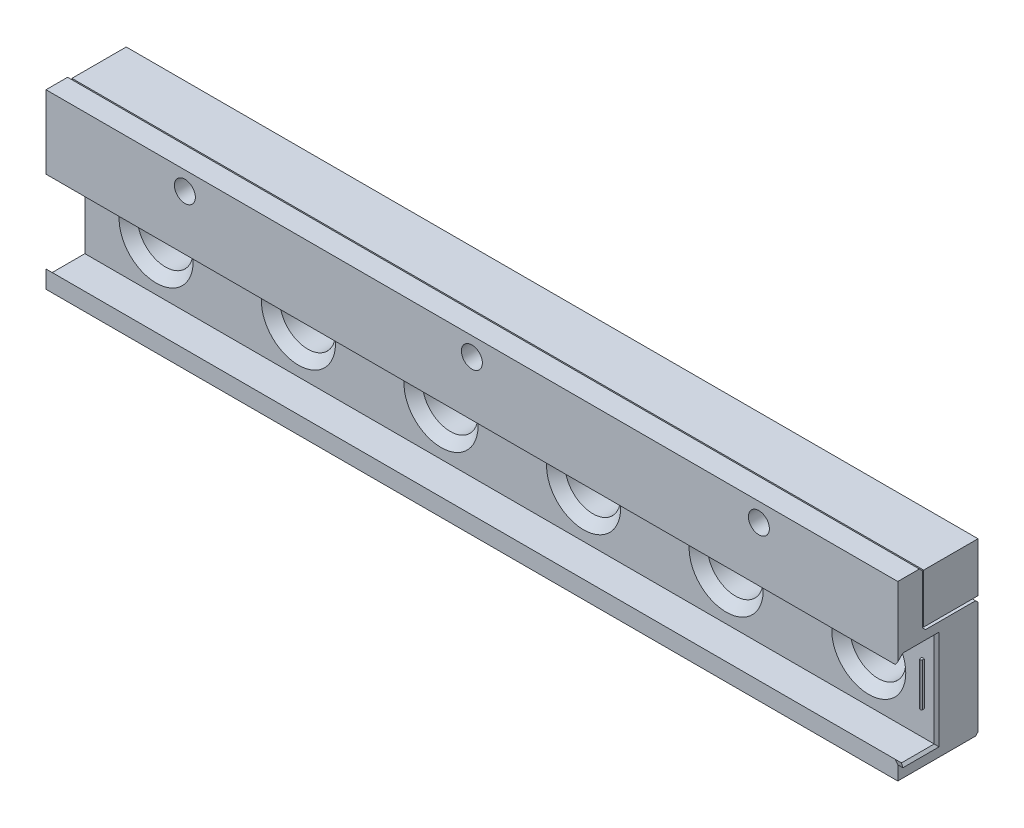
SolidWorks part; units mm, degrees
ref_plane "Front Plane" through (0, 0, 0) normal (0, 0, 1) x (1, 0, 0)
ref_plane "Top Plane" through (0, 0, 0) normal (0, 1, 0) x (1, 0, 0)
ref_plane "Right Plane" through (0, 0, 0) normal (1, 0, 0) x (0, 0, -1)
sketch "Sketch1" plane through (0, 0, 0) normal (0, 0, 1) x (1, 0, 0)
  line L1 (-107.1072, 25.5521) -> (30.8928, 25.5521)
  line L2 (-107.1072, 25.5521) -> (-107.1072, 6.5521)
  line L3 (-107.1072, 6.5521) -> (30.8928, 6.5521)
  line L4 (30.8928, 25.5521) -> (30.8928, 6.5521)
  dimension "D1" = 138
  dimension "D2" = 19
extrude "Boss-Extrude1" add sketch "Sketch1" along normal blind 13
sketch "Sketch2" plane through (0, 0, 13) normal (0, 0, 1) x (1, 0, 0)
  line L0 (-107.1072, 25.5521) -> (-107.1072, 6.5521) construction
  line L1 (-107.1072, 6.5521) -> (30.8928, 6.5521) construction
  circle A0 centre (-95.5572, 16.0521) radius 4.5
  dimension "D1" = 9
  dimension "D2" = 11.55
  dimension "D3" = 9.5
extrude "Cut-Extrude1" cut sketch "Sketch2" against normal through all
sketch "Sketch4" plane through (0, 0, 13) normal (0, 0, 1) x (1, 0, 0)
  line L0 (-107.1072, 6.5521) -> (30.8928, 6.5521) construction
  circle A0 centre (-72.5072, 16.0521) radius 4.5
  circle A1 centre (-95.5572, 16.0521) radius 4.5 construction
  dimension "D2" = 9
  dimension "D1" = 23.05
  dimension "D3" = 9.5
extrude "Cut-Extrude2" cut sketch "Sketch4" against normal through all
sketch "Sketch5" plane through (0, 0, 13) normal (0, 0, 1) x (1, 0, 0)
  line L0 (-107.1072, 6.5521) -> (30.8928, 6.5521) construction
  circle A0 centre (-49.4072, 16.0521) radius 4.5
  circle A1 centre (-72.5072, 16.0521) radius 4.5 construction
  dimension "D2" = 9
  dimension "D1" = 23.1
  dimension "D3" = 9.5
extrude "Cut-Extrude3" cut sketch "Sketch5" against normal through all
sketch "Sketch6" plane through (0, 0, 13) normal (0, 0, 1) x (1, 0, 0)
  line L0 (-107.1072, 6.5521) -> (30.8928, 6.5521) construction
  circle A0 centre (-26.3072, 16.0521) radius 4.5
  circle A1 centre (-49.4072, 16.0521) radius 4.5 construction
  circle A2 centre (-3.2072, 16.0521) radius 4.5
  circle A3 centre (19.8928, 16.0521) radius 4.5
  dimension "D3" = 9
  dimension "D6" = 9
  dimension "D9" = 9
  dimension "D1" = 23.1
  dimension "D2" = 9.5
  dimension "D4" = 23.1
  dimension "D5" = 9.5
  dimension "D7" = 23.1
  dimension "D8" = 9.5
extrude "Cut-Extrude4" cut sketch "Sketch6" against normal through all
sketch "Sketch7" plane through (0, 0, 13) normal (0, 0, 1) x (1, 0, 0)
  line L0 (-107.1072, 25.5521) -> (-107.1072, 6.5521) construction
  line L1 (-107.1072, 23.7021) -> (30.8928, 23.7021)
  line L2 (-107.1072, 23.7021) -> (-107.1072, 8.4021)
  line L3 (-107.1072, 8.4021) -> (30.8928, 8.4021)
  line L4 (30.8928, 23.7021) -> (30.8928, 8.4021)
  line L5 (30.8928, 6.5521) -> (30.8928, 25.5521) construction
  line L6 (30.8928, 25.5521) -> (-107.1072, 25.5521) construction
  line L7 (-107.1072, 6.5521) -> (30.8928, 6.5521) construction
  dimension "D1" = 1.85
  dimension "D2" = 1.85
extrude "Cut-Extrude5" cut sketch "Sketch7" against normal blind 6.3
sketch "Sketch11" plane through (0, 25.5521, 0) normal (0, 1, 0) x (1, 0, 0)
  line L0 (30.8928, -13) -> (30.8928, 0) construction
  line L1 (-107.1072, -13) -> (30.8928, -13)
  line L2 (-107.1072, -13) -> (-107.1072, -9)
  line L3 (-107.1072, -9) -> (30.8928, -9)
  line L4 (30.8928, -13) -> (30.8928, -9)
  dimension "D1" = 4
extrude "Boss-Extrude4" add sketch "Sketch11" along normal blind 9
sketch "Sketch12" plane through (0, 0, 13) normal (0, 0, 1) x (1, 0, 0)
  line L0 (-107.1072, 34.5521) -> (30.8928, 34.5521) construction
  line L1 (-107.1072, 34.5521) -> (-107.1072, 23.7021) construction
  circle A0 centre (-84.6072, 31.5521) radius 1.7
  dimension "D1" = 3.4
  dimension "D2" = 3
  dimension "D3" = 22.5
extrude "Cut-Extrude6" cut sketch "Sketch12" against normal through all
sketch "Sketch13" plane through (0, 0, 13) normal (0, 0, 1) x (1, 0, 0)
  line L0 (-107.1072, 34.5521) -> (30.8928, 34.5521) construction
  line L1 (30.8928, 23.7021) -> (30.8928, 34.5521) construction
  circle A0 centre (8.3928, 31.5521) radius 1.7
  dimension "D1" = 3.4
  dimension "D2" = 3
  dimension "D3" = 22.5
extrude "Cut-Extrude7" cut sketch "Sketch13" against normal through all
chamfer "Chamfer1" distance 0.4 angle 45 2 edges at (-38.1072, 25.5521, 0) (-38.1072, 6.5521, 0)
chamfer "Chamfer2" distance 0.5 angle 45 2 edges at (-82.9072, 31.5521, 9) (10.0928, 31.5521, 9)
chamfer "Chamfer3" distance 0.5 angle 45 1 edges at (-38.1072, 25.5521, 9)
chamfer "Chamfer4" distance 0.5 angle 45 1 edges at (-38.1072, 34.5521, 9)
sketch "Sketch14" plane through (0, 0, 0) normal (0, 0, -1) x (-1, 0, 0)
  line L1 (-30.8928, 34.0521) -> (107.1072, 34.0521)
  line L2 (-30.8928, 34.0521) -> (-30.8928, 26.0521)
  line L3 (-30.8928, 26.0521) -> (107.1072, 26.0521)
  line L4 (107.1072, 34.0521) -> (107.1072, 26.0521)
extrude "Boss-Extrude5" add sketch "Sketch14" against normal blind 8.8 separate body
sketch "Sketch15" plane through (0, 0, 8.8) normal (0, 0, 1) x (1, 0, 0)
  line L0 (-107.1072, 34.0521) -> (30.8928, 34.0521) construction
  line L1 (-106.1072, 33.0521) -> (29.8928, 33.0521)
  line L2 (-106.1072, 33.0521) -> (-106.1072, 27.0521)
  line L3 (-106.1072, 27.0521) -> (29.8928, 27.0521)
  line L4 (29.8928, 33.0521) -> (29.8928, 27.0521)
  line L5 (30.8928, 26.0521) -> (-107.1072, 26.0521) construction
  line L6 (-107.1072, 26.0521) -> (-107.1072, 34.0521) construction
  line L7 (30.8928, 34.0521) -> (30.8928, 26.0521) construction
  dimension "D1" = 1
  dimension "D2" = 1
  dimension "D3" = 1
  dimension "D4" = 1
extrude "Cut-Extrude8" cut sketch "Sketch15" against normal blind 1
chamfer "Chamfer5" distance 1.5 angle 45 4 edges at (-21.8072, 16.0521, 6.7) (-44.9072, 16.0521, 6.7) (-68.0072, 16.0521, 6.7) (-91.0572, 16.0521, 6.7)
sketch "Sketch19" plane through (30.8928, 0, 0) normal (1, 0, 0) x (0, 0, -1)
  line L0 (-13, 23.7021) -> (-12, 23.7021)
  line L1 (-6.7, 23.7021) -> (-13, 23.7021) construction
  line L2 (-12, 23.7021) -> (-13, 22.7021)
  line L3 (-13, 22.7021) -> (-13, 23.7021)
  line L4 (-13, 8.4021) -> (-12, 8.4021)
  line L5 (-6.7, 8.4021) -> (-13, 8.4021) construction
  line L6 (-12, 8.4021) -> (-13, 9.4021)
  line L7 (-13, 9.4021) -> (-13, 8.4021)
  dimension "D1" = 1
  dimension "D2" = 1
  dimension "D3" = 1
extrude "Boss-Extrude8" add sketch "Sketch19" against normal up to surface (138 mm away) up to face at (-107.1072, 20.695, 7.3)
sketch "Sketch20" plane through (0, 0, 6.7) normal (0, 0, 1) x (1, 0, 0)
  line L1 (28.4928, 19.5521) -> (28.8928, 19.5521)
  line L2 (28.4928, 19.5521) -> (28.4928, 12.5521)
  line L3 (28.4928, 12.5521) -> (28.8928, 12.5521)
  line L4 (28.8928, 19.5521) -> (28.8928, 12.5521)
  line L5 (30.8928, 23.7021) -> (-107.1072, 23.7021) construction
  line L6 (30.8928, 8.4021) -> (30.8928, 23.7021) construction
  dimension "D1" = 0.4
  dimension "D2" = 7
  dimension "D3" = 2
  dimension "D4" = 4.15
chamfer "Chamfer6" distance 0.4 angle 45 5 edges at (30.8928, 23.2021, 12.5) (30.8928, 23.7021, 9.35) (30.8928, 16.0521, 6.7) (30.8928, 8.4021, 9.35) (30.8928, 8.9021, 12.5)
extrude "Boss-Extrude9" add sketch "Sketch20" along normal blind 0.75
fillet "Fillet1" radius 0.5 1 edges at (28.4928, 16.0521, 7.45)
fillet "Fillet2" radius 0.2 1 edges at (28.8928, 16.0521, 7.45)
chamfer "Chamfer7" distance 1.5 angle 45 2 edges at (24.3928, 16.0521, 6.7) (1.2928, 16.0521, 6.7)
sketch "Sketch25" plane through (0, 0, 13) normal (0, 0, 1) x (1, 0, 0)
  line L0 (-107.1072, 34.5521) -> (30.8928, 34.5521) construction
  circle A2 centre (-38.1072, 31.5521) radius 1.7
  dimension "D2" = 3.4
  dimension "D3" = 3
extrude "Cut-Extrude9" cut sketch "Sketch25" against normal blind 4
chamfer "Chamfer8" distance 0.4 angle 45 1 edges at (-36.4072, 31.5521, 9)
sketch "Sketch26" plane through (0, 0, 0) normal (0, 0, -1) x (-1, 0, 0)
  line L0 (107.1072, 34.0521) -> (-30.8928, 34.0521) construction
  line L1 (-29.8928, 33.0521) -> (106.1072, 33.0521)
  line L2 (-29.8928, 33.0521) -> (-29.8928, 27.0521)
  line L3 (-29.8928, 27.0521) -> (106.1072, 27.0521)
  line L4 (106.1072, 33.0521) -> (106.1072, 27.0521)
  line L5 (-30.8928, 26.0521) -> (107.1072, 26.0521) construction
  line L6 (-30.8928, 34.0521) -> (-30.8928, 26.0521) construction
  line L7 (107.1072, 26.0521) -> (107.1072, 34.0521) construction
  dimension "D1" = 1
  dimension "D2" = 1
  dimension "D3" = 1
  dimension "D4" = 1
extrude "Cut-Extrude10" cut sketch "Sketch26" against normal blind 7
sketch "Sketch27" plane through (0, 0, 8.8) normal (0, 0, 1) x (1, 0, 0)
  line L0 (-106.1072, 33.0521) -> (-105.1072, 33.0521)
  line L1 (29.8928, 33.0521) -> (-106.1072, 33.0521) construction
  line L2 (-105.1072, 33.0521) -> (-100.906, 27.0521)
  line L3 (-106.1072, 27.0521) -> (29.8928, 27.0521) construction
  line L4 (-100.906, 27.0521) -> (-101.906, 27.0521)
  line L5 (-106.1072, 27.0521) -> (29.8928, 27.0521) construction
  line L6 (-101.906, 27.0521) -> (-106.1072, 33.0521)
  line L7 (-106.1072, 33.0521) -> (-106.1072, 27.0521) construction
  dimension "D1" = 1
  dimension "D2" = 1
  dimension "D3" = 35
extrude "Boss-Extrude10" add sketch "Sketch27" against normal up to surface (1 mm away) up to face at (-38.1072, 30.0521, 7.8)
sketch "Sketch28" plane through (0, 0, 8.8) normal (0, 0, 1) x (1, 0, 0)
  line L0 (-106.1072, 27.0521) -> (-105.1072, 27.0521)
  line L1 (-106.1072, 27.0521) -> (-101.906, 27.0521) construction
  line L2 (-105.1072, 27.0521) -> (-100.906, 33.0521)
  line L3 (29.8928, 33.0521) -> (-105.1072, 33.0521) construction
  line L4 (-100.906, 33.0521) -> (-101.906, 33.0521)
  line L5 (29.8928, 33.0521) -> (-105.1072, 33.0521) construction
  line L6 (-101.906, 33.0521) -> (-106.1072, 27.0521)
  line L7 (-106.1072, 33.0521) -> (-106.1072, 27.0521) construction
  dimension "D1" = 1
  dimension "D2" = 1
  dimension "D3" = 35
extrude "Boss-Extrude11" add sketch "Sketch28" against normal up to surface (1 mm away) up to face at (-36.5569, 30.0521, 7.8)
pattern_linear "LPattern1" count 27 spacing 5.2 along (1, 0, 0) of "Boss-Extrude11", "Boss-Extrude10"
sketch "Sketch29" plane through (30.8928, 0, 0) normal (1, 0, 0) x (0, 0, -1)
  line L0 (-8.8, 26.0521) -> (0, 26.0521) construction
  line L1 (-8.8, 34.0521) -> (-7.7774, 34.0521)
  line L2 (-8.8, 34.0521) -> (-8.8, 26.0521)
  line L3 (-8.8, 26.0521) -> (-7.7774, 26.0521)
  line L4 (-7.7774, 34.0521) -> (-7.7774, 26.0521)
extrude "Cut-Extrude11" cut sketch "Sketch29" along normal blind 6.9
sketch "Sketch30" plane through (0, 0, 0) normal (0, 0, -1) x (-1, 0, 0)
  line L0 (106.1072, 33.0521) -> (-29.8928, 33.0521) construction
  line L1 (-26.8928, 33.0521) -> (-25.8928, 33.0521)
  line L2 (-26.8928, 33.0521) -> (-26.8928, 27.0521)
  line L3 (-26.8928, 27.0521) -> (-25.8928, 27.0521)
  line L4 (-25.8928, 33.0521) -> (-25.8928, 27.0521)
  line L5 (-29.8928, 27.0521) -> (106.1072, 27.0521) construction
  line L6 (-29.8928, 33.0521) -> (-29.8928, 27.0521) construction
  dimension "D1" = 1
  dimension "D2" = 3
extrude "Boss-Extrude12" add sketch "Sketch30" against normal up to surface (7 mm away) up to face at (-38.1072, 30.0521, 7)
pattern_linear "LPattern2" count 33 spacing 4.05 along (-1, 0, 0) of "Boss-Extrude12"
sketch "Sketch31" plane through (0, 0, 8.8) normal (0, 0, 1) x (1, 0, 0)
  circle A0 centre (-84.6072, 31.5521) radius 2.5
  circle A1 centre (-38.1072, 31.5521) radius 2.5
  circle A2 centre (8.3928, 31.5521) radius 2.5
extrude "Boss-Extrude13" add sketch "Sketch31" against normal blind 1
